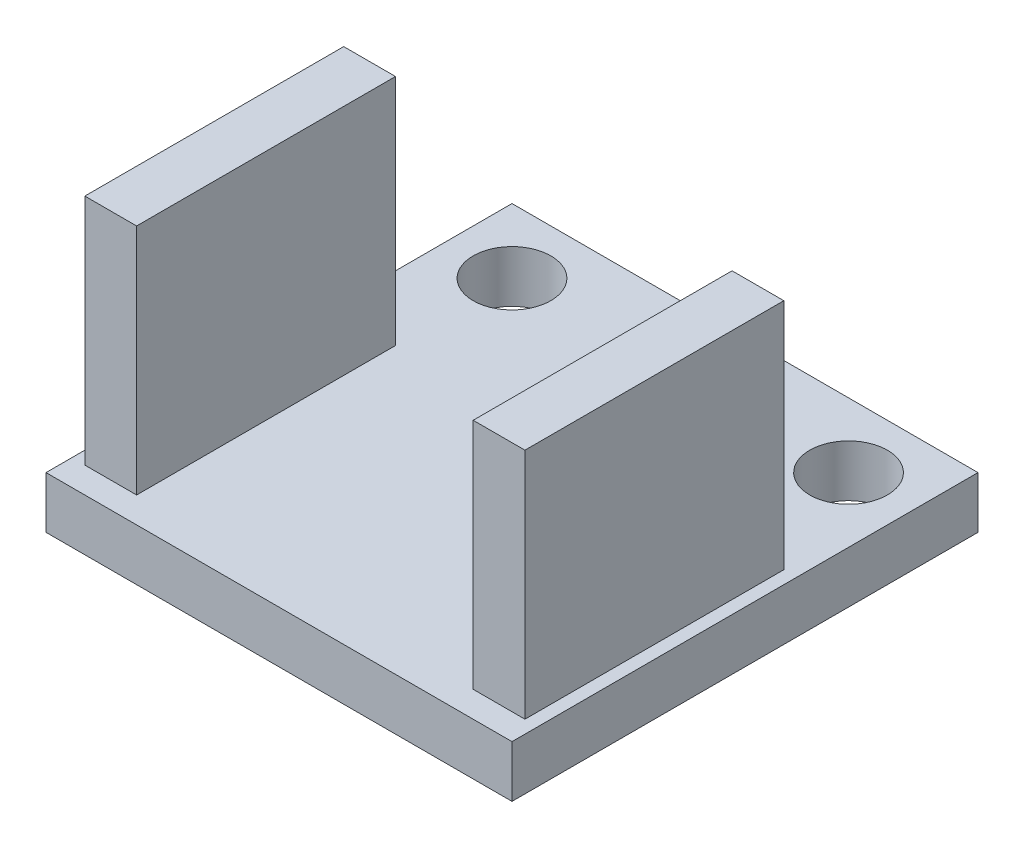
SolidWorks part; units mm, degrees
ref_plane "Front Plane" through (0, 0, 0) normal (0, 0, 1) x (1, 0, 0)
ref_plane "Top Plane" through (0, 0, 0) normal (0, 1, 0) x (1, 0, 0)
ref_plane "Right Plane" through (0, 0, 0) normal (1, 0, 0) x (0, 0, -1)
sketch "Sketch1" plane through (0, 0, 0) normal (0, 1, 0) x (1, 0, 0)
  line L1 (0, 0) -> (18, 0)
  line L2 (0, 0) -> (0, -18)
  line L3 (0, -18) -> (18, -18)
  line L4 (18, 0) -> (18, -18)
  dimension "D1" = 18
extrude "Boss-Extrude1" add sketch "Sketch1" along normal blind 2
sketch "Sketch2" plane through (0, 2, 0) normal (0, 1, 0) x (1, 0, 0)
  line L0 (18, 0) -> (0, 0) construction
  line L1 (0, 0) -> (0, -18) construction
  line L2 (18, -18) -> (18, 0) construction
  circle A0 centre (2.5, -2.5) radius 1.5
  circle A1 centre (15.5, -2.5) radius 1.5
  dimension "D1" = 3
  dimension "D2" = 2.5
  dimension "D3" = 2.5
  dimension "D4" = 2.5
  dimension "D5" = 2.5
extrude "Cut-Extrude1" cut sketch "Sketch2" against normal blind 2
sketch "Sketch3" plane through (0, 2, 0) normal (0, 1, 0) x (1, 0, 0)
  line L0 (0, -18) -> (18, -18) construction
  line L5 (0.5, -7) -> (2.5, -7)
  line L6 (0.5, -7) -> (0.5, -17)
  line L7 (0.5, -17) -> (2.5, -17)
  line L8 (2.5, -7) -> (2.5, -17)
  line L9 (15.5, -7) -> (17.5, -7)
  line L10 (15.5, -7) -> (15.5, -17)
  line L11 (15.5, -17) -> (17.5, -17)
  line L12 (17.5, -7) -> (17.5, -17)
  line L13 (0, 0) -> (0, -18) construction
  line L14 (18, -18) -> (18, 0) construction
  point P12 (16.5, -17)
  dimension "D1" = 10
  dimension "D2" = 1
  dimension "D3" = 0.5
  dimension "D4" = 2
  dimension "D5" = 1
  dimension "D6" = 0.5
  dimension "D7" = 2
  dimension "D8" = 10
extrude "Boss-Extrude2" add sketch "Sketch3" along normal blind 9
